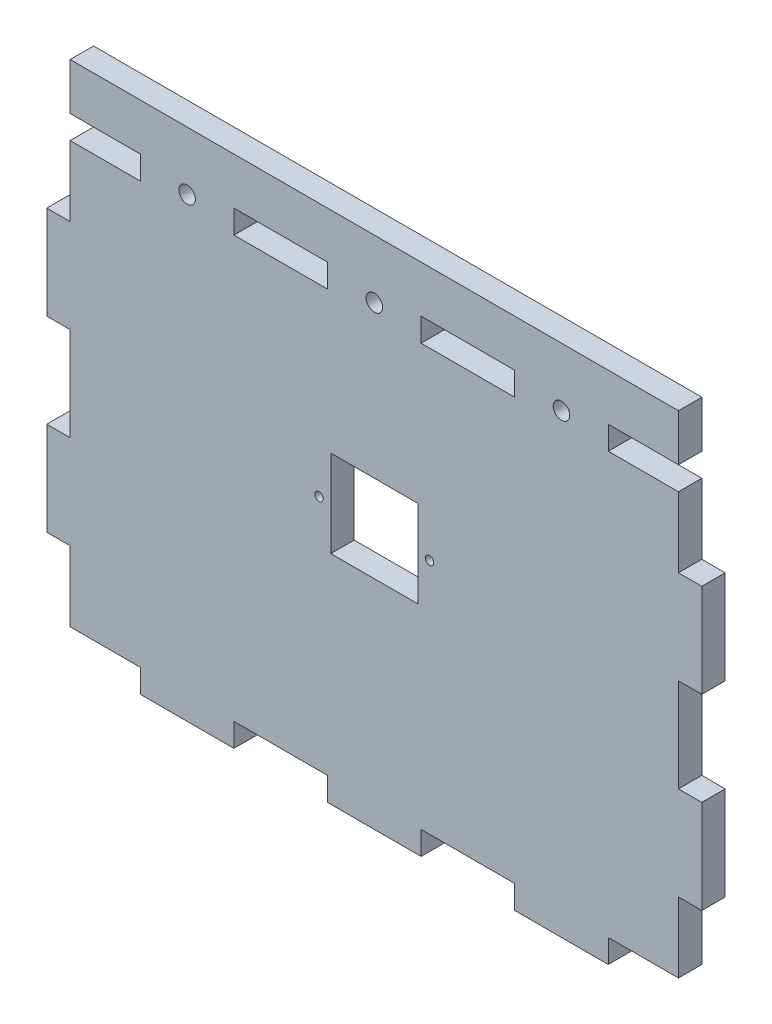
SolidWorks part; units mm, degrees
ref_plane "Front Plane" through (0, 0, 0) normal (0, 0, 1) x (1, 0, 0)
ref_plane "Top Plane" through (0, 0, 0) normal (0, 1, 0) x (1, 0, 0)
ref_plane "Right Plane" through (0, 0, 0) normal (1, 0, 0) x (0, 0, -1)
sketch "Sketch1" plane through (0, 0, 0) normal (0, 0, 1) x (1, 0, 0)
  line L1 (0, 0) -> (177.8, 0)
  line L2 (0, 0) -> (0, 139.7)
  line L3 (0, 139.7) -> (177.8, 139.7)
  line L4 (177.8, 0) -> (177.8, 139.7)
  dimension "D1" = 177.8
  dimension "D2" = 139.7
extrude "Boss-Extrude1" add sketch "Sketch1" along normal blind 6.35
sketch "Sketch5" plane through (0, 0, 6.35) normal (0, 0, 1) x (1, 0, 0)
  line L1 (0, 0) -> (6.35, 0)
  line L2 (0, 0) -> (0, 25.4)
  line L3 (0, 25.4) -> (6.35, 25.4)
  line L4 (6.35, 0) -> (6.35, 25.4)
  dimension "D1" = 25.4
  dimension "D2" = 6.35
extrude "Cut-Extrude4" cut sketch "Sketch5" against normal blind 6.35
sketch "Sketch6" plane through (0, 0, 6.35) normal (0, 0, 1) x (1, 0, 0)
  line L1 (0, 0) -> (25.4, 0)
  line L2 (0, 0) -> (0, 6.35)
  line L3 (0, 6.35) -> (25.4, 6.35)
  line L4 (25.4, 0) -> (25.4, 6.35)
  dimension "D1" = 6.35
  dimension "D2" = 25.4
extrude "Cut-Extrude5" cut sketch "Sketch6" against normal blind 6.35
pattern_linear "LPattern5" count 3 spacing 50.8 along (0, 1, 0) count 2 spacing 171.45 along (1, 0, 0) of "Cut-Extrude4"
pattern_linear "LPattern6" count 4 spacing 50.8 along (1, 0, 0) count 2 spacing 120.65 along (0, 1, 0) of "Cut-Extrude5"
sketch "Sketch7" plane through (0, 0, 6.35) normal (0, 0, 1) x (1, 0, 0)
  line L1 (6.35, 120.65) -> (0, 120.65)
  line L2 (6.35, 120.65) -> (6.35, 139.7)
  line L3 (6.35, 139.7) -> (0, 139.7)
  line L4 (0, 120.65) -> (0, 139.7)
  dimension "D1" = 6.35
  dimension "D2" = 19.05
extrude "Cut-Extrude6" cut sketch "Sketch7" against normal blind 6.35
sketch "Sketch12" plane through (0, 0, 6.35) normal (0, 0, 1) x (1, 0, 0)
  line L0 (177.8, 127) -> (177.8, 139.7) construction
  line L1 (177.8, 139.7) -> (171.45, 139.7)
  line L2 (177.8, 139.7) -> (177.8, 127)
  line L3 (177.8, 127) -> (171.45, 127)
  line L4 (171.45, 139.7) -> (171.45, 127)
  line L5 (177.8, 139.7) -> (6.35, 139.7) construction
  dimension "D1" = 6.35
  dimension "D2" = 12.7
extrude "Cut-Extrude9" cut sketch "Sketch12" against normal blind 7.62
hole_wizard "#8 Clearance Hole1" positions "Sketch10" profile "Sketch9" hole size "#8" standard "ANSI Inch"
sketch "Sketch10" plane through (0, 0, 6.35) normal (0, 0, 1) x (1, 0, 0)
  line L2 (25.4, 120.65) -> (25.4, 127) construction
  line L3 (76.2, 127) -> (50.8, 127) construction
  line L4 (127, 120.65) -> (127, 127) construction
  point P0 (38.1, 123.825)
  point P2 (88.9, 123.825)
  point P10 (25.4, 123.825)
  point P16 (139.7, 123.825)
  dimension "D1" = 12.7
  dimension "D2" = 12.7
  dimension "D3" = 12.7
  dimension "D4" = 3.175
sketch "Sketch9" plane through (38.1, 123.825, 6.35) normal (1, 0, 0) x (0, -1, 0)
  line L0 (0, 0) -> (0, 11.5107)
  line L1 (0, 11.5107) -> (2.2479, 10.16)
  line L2 (2.2479, 10.16) -> (2.2479, 0)
  line L5 (2.2479, 0) -> (0, 0)
  line L10 (0, 11.5107) -> (-2.2479, 10.16) construction
  line L11 (0, -6.35) -> (0, 107.95) construction
  dimension "Hole Dia." = 4.4958
  dimension "Hole Depth" = 10.16
  dimension "Drill Angle" = 118
sketch "Sketch11" plane through (0, 0, 6.35) normal (0, 0, 1) x (1, 0, 0)
  line L1 (77.089, 82.55) -> (100.711, 82.55)
  line L2 (77.089, 82.55) -> (77.089, 58.928)
  line L3 (77.089, 58.928) -> (100.711, 58.928)
  line L4 (100.711, 82.55) -> (100.711, 58.928)
  line L6 (0, 101.6) -> (0, 76.2) construction
  line L7 (50.8, 120.65) -> (76.2, 120.65) construction
  circle A0 centre (73.914, 70.739) radius 1.143
  circle A1 centre (103.886, 70.739) radius 1.143
  point P6 (88.9, 82.55)
  point P13 (100.711, 70.739)
  point P14 (77.089, 70.739)
  dimension "D5" = 2.286
  dimension "D6" = 2.286
  dimension "D7" = 14.986
  dimension "D8" = 14.986
  dimension "D1" = 38.1
  dimension "D2" = 23.622
  dimension "D3" = 23.622
  dimension "D4" = 88.9
extrude "Cut-Extrude8" cut sketch "Sketch11" against normal blind 7.62
